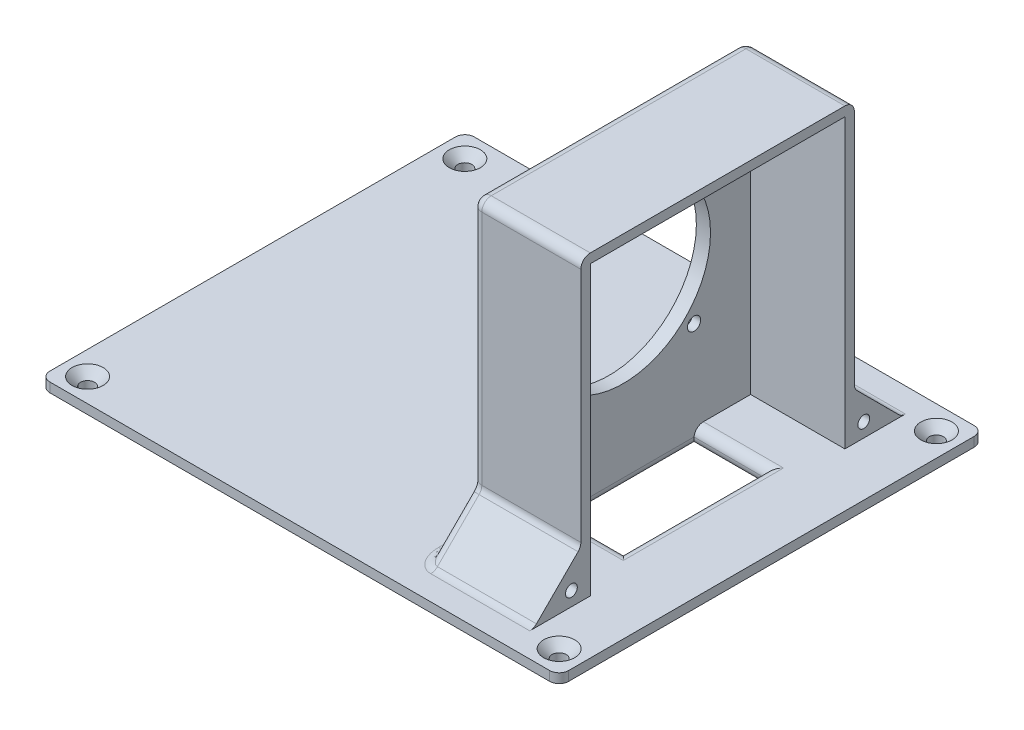
SolidWorks part; units mm, degrees
ref_plane "Front Plane" through (0, 0, 0) normal (0, 0, 1) x (1, 0, 0)
ref_plane "Top Plane" through (0, 0, 0) normal (0, 1, 0) x (1, 0, 0)
ref_plane "Right Plane" through (0, 0, 0) normal (1, 0, 0) x (0, 0, -1)
sketch "Sketch1" plane through (0, 0, 0) normal (0, 1, 0) x (1, 0, 0)
  line L1 (-55, 45) -> (55, 45)
  line L2 (-55, 45) -> (-55, -45)
  line L3 (-55, -45) -> (55, -45)
  line L4 (55, 45) -> (55, -45)
  line L5 (-55, 45) -> (55, -45) construction
  line L6 (-55, -45) -> (55, 45) construction
  point P0 (0, 0)
  dimension "D1" = 110
  dimension "D2" = 90
extrude "Boss-Extrude1" add sketch "Sketch1" along normal blind 2
sketch "Sketch2" plane through (0, 0, 0) normal (0, -1, 0) x (1, 0, 0)
  line L0 (-55, -45) -> (-55, 45) construction
  line L1 (-52.8, 42.8) -> (52.8, 42.8)
  line L2 (-52.8, 42.8) -> (-52.8, -42.8)
  line L3 (-52.8, -42.8) -> (52.8, -42.8)
  line L4 (52.8, 42.8) -> (52.8, -42.8)
  line L5 (-52.8, 42.8) -> (52.8, -42.8) construction
  line L6 (-52.8, -42.8) -> (52.8, 42.8) construction
  line L7 (-55, 45) -> (55, 45) construction
  point P0 (0, 0)
  dimension "D1" = 2.2
  dimension "D2" = 2.2
extrude "Boss-Extrude2" add sketch "Sketch2" along normal blind 1.8
fillet "Fillet1" radius 2 4 edges at (-52.8, -0.9, -42.8) (52.8, -0.9, -42.8) (52.8, -0.9, 42.8) (-52.8, -0.9, 42.8)
fillet "Fillet2" radius 2 4 edges at (55, 1, 45) (-55, 1, 45) (-55, 1, -45) (55, 1, -45)
sketch "Sketch3" plane through (0, 2, 0) normal (0, 1, 0) x (1, 0, 0)
  circle A0 centre (-50, 40) radius 1.5
  circle A1 centre (50, 40) radius 1.5
  circle A2 centre (-50, -40) radius 1.5
  circle A3 centre (50, -40) radius 1.5
extrude "Cut-Extrude1" cut sketch "Sketch3" against normal through all
chamfer "Chamfer1" distance 1.8 angle 45 4 edges at (-50, 2, -38.5) (50, 2, -38.5) (50, 2, 41.5) (-50, 2, 41.5)
ref_plane "Plane1" through (23.6, 0, 0) normal (-1, 0, 0) x (0, 0, 1)
sketch "Sketch5" plane through (23.6, 0, 0) normal (-1, 0, 0) x (0, 0, 1)
  line L0 (0, 2) -> (0, 68.8245) construction
  line L1 (-43, 2) -> (43, 2) construction
  line L2 (-29, 2) -> (-29, 65)
  line L3 (-29, 65) -> (29, 65)
  line L4 (29, 2) -> (29, 65)
  line L5 (-29, 2) -> (29, 2)
  line L6 (-19, 19.5) -> (-19, 52.5) construction
  line L7 (-16.5, 55) -> (16.5, 55) construction
  point P9 (0, 65)
  dimension "D1" = 10
  dimension "D2" = 10
extrude "Boss-Extrude3" add sketch "Sketch5" along normal blind 3
sketch "Sketch6" plane through (20.6, 0, 0) normal (-1, 0, 0) x (0, 0, 1)
  circle A0 centre (0, 36) radius 18.5
  dimension "D1" = 37
extrude "Cut-Extrude2" cut sketch "Sketch6" against normal up to next
sketch "Sketch7" plane through (20.6, 0, 0) normal (-1, 0, 0) x (0, 0, 1)
  line L0 (0, 17.5) -> (0, 54.5) construction
  line L2 (-5.5, 58.5) -> (5.5, 58.5)
  line L3 (-5.5, 58.5) -> (-5.5, 50.5)
  line L4 (-5.5, 50.5) -> (5.5, 50.5)
  line L5 (5.5, 58.5) -> (5.5, 50.5)
  line L6 (-5.5, 58.5) -> (5.5, 50.5) construction
  line L7 (-5.5, 50.5) -> (5.5, 58.5) construction
  line L8 (-21.6266, 36) -> (21.6266, 36) construction
  circle A0 centre (0, 36) radius 18.5 construction
  circle A1 centre (-15, 51) radius 1.4
  circle A2 centre (15, 51) radius 1.4
  circle A3 centre (15, 21) radius 1.4
  circle A4 centre (-15, 21) radius 1.4
  point P19 (0, 36)
  dimension "D3" = 2.8
  dimension "D4" = 30
  dimension "D1" = 8
  dimension "D2" = 11
  dimension "D5" = 30
extrude "Cut-Extrude3" cut sketch "Sketch7" against normal up to next
sketch "Sketch8" plane through (23.6, 0, 0) normal (1, 0, 0) x (0, 0, -1)
  line L0 (29, 65) -> (29, 2) construction
  line L1 (-29, 65) -> (29, 65) construction
  line L2 (-29, 2) -> (-29, 65) construction
  line L3 (29, 65) -> (29, 2)
  line L4 (-29, 65) -> (29, 65)
  line L5 (-29, 2) -> (-29, 65)
  line L6 (-27, 2) -> (-27, 63)
  line L7 (-27, 63) -> (27, 63)
  line L8 (27, 63) -> (27, 2)
  line L9 (-29, 2) -> (-27, 2)
  line L10 (29, 2) -> (27, 2)
  dimension "D1" = 2
extrude "Boss-Extrude4" add sketch "Sketch8" along normal blind 20
chamfer "Chamfer2" distance 10 angle 45 2 edges at (32.1, 2, -29) (32.1, 2, 29)
fillet "Fillet3" radius 2 12 edges at (32.1, 2, -39) (32.1, 2, 39) (32.1, 12, -29) (20.6, 2, 0) (20.6, 7, -34) (20.6, 38.5, -29) (32.1, 65, -29) (20.6, 65, 0) (32.1, 65, 29) (32.1, 12, 29) (20.6, 7, 34) (20.6, 38.5, 29)
sketch "Sketch9" plane through (43.6, 0, 0) normal (1, 0, 0) x (0, 0, -1)
  line L0 (-43, 2) -> (43, 2) construction
  line L1 (0, 2) -> (0, 39.1972) construction
  circle A0 centre (-31, 5) radius 1.25
  circle A1 centre (31, 5) radius 1.25
  dimension "D1" = 2.5
  dimension "D2" = 3
  dimension "D3" = 62
extrude "Cut-Extrude4" cut sketch "Sketch9" against normal blind 10
sketch "Sketch10" plane through (0, 2, 0) normal (0, 1, 0) x (1, 0, 0)
  line L0 (22.6, 0) -> (55, 0) construction
  line L1 (22.6, 27) -> (22.6, -27) construction
  line L2 (55, -43) -> (55, 43) construction
  line L4 (23.6, 15) -> (38.6, 15)
  line L5 (23.6, 15) -> (23.6, -15)
  line L6 (23.6, -15) -> (38.6, -15)
  line L7 (38.6, 15) -> (38.6, -15)
  line L8 (23.6, 15) -> (38.6, -15) construction
  line L9 (23.6, -15) -> (38.6, 15) construction
  point P6 (31.1, 0)
  dimension "D1" = 30
  dimension "D2" = 15
  dimension "D3" = 8.5
extrude "Cut-Extrude5" cut sketch "Sketch10" against normal up to next
fillet "Fillet5" radius 2 4 edges at (31.1, -1.8, -15) (38.6, -1.8, 0) (31.1, -1.8, 15) (23.6, -1.8, 0)
fillet "Fillet6" radius 2 3 edges at (31.1, 2, 15) (31.1, 2, -15) (38.6, 2, 0)
chamfer "Chamfer3" distance 1.2 angle 45 4 edges at (20.6, 22.4, -15) (20.6, 19.6, 15) (20.6, 49.6, -15) (20.6, 52.4, 15)
